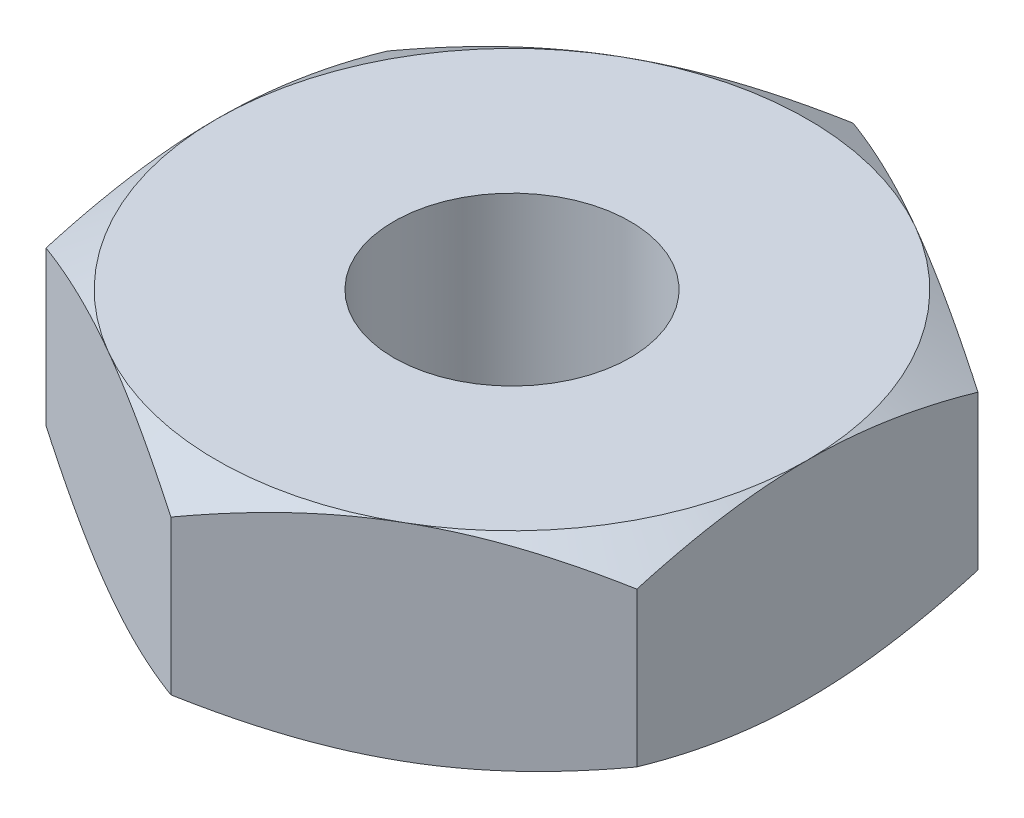
SolidWorks part; units mm, degrees
material "AISI 316 Stainless Steel Sheet (SS)"
ref_plane "Front Plane" through (0, 0, 0) normal (0, 0, 1) x (1, 0, 0)
ref_plane "Top Plane" through (0, 0, 0) normal (0, 1, 0) x (1, 0, 0)
ref_plane "Right Plane" through (0, 0, 0) normal (1, 0, 0) x (0, 0, -1)
sketch "Sketch1" plane through (0, 0, 0) normal (0, 1, 0) x (1, 0, 0)
  line L1 (-3.9688, 2.2914) -> (-3.9688, -2.2914)
  line L2 (-3.9688, -2.2914) -> (0, -4.5827)
  line L3 (0, -4.5827) -> (3.9687, -2.2914)
  line L4 (3.9687, -2.2914) -> (3.9688, 2.2914)
  line L5 (3.9688, 2.2914) -> (0, 4.5827)
  line L6 (0, 4.5827) -> (-3.9688, 2.2914)
  circle A0 centre (0, 0) radius 3.9688 construction
  circle A1 centre (0, 0) radius 1.5875
  dimension "Thread Size" = 3.175
  dimension "Hex" = 7.9375
extrude "Boss-Extrude1" add sketch "Sketch1" along normal mid plane 2.7781
sketch "Sketch2" plane through (0, 1.3891, 0) normal (0, 1, 0) x (1, 0, 0)
  circle A0 centre (0, 0) radius 1.5875 construction
  circle A1 centre (0, 0) radius 1.5875
curve "Helix/Spiral1" [suppressed] pitch 0.635 height 3.4131 turns 5.375 parameters "Pitch"=0.635
sketch "Sketch3" plane through (0, 0, 0) normal (1, 0, 0) x (0, 0, -1)
  line L0 (1.1751, 1.7066) -> (1.5875, 1.9447)
  line L1 (1.5875, 1.9447) -> (1.5875, 1.3891)
  line L2 (1.5875, 1.3891) -> (1.1751, 1.6272)
  line L3 (1.1751, 1.6272) -> (1.1751, 1.7066)
  line L4 (1.3813, 1.8256) -> (1.3813, 1.5081) construction
  line L5 (1.1751, 1.6669) -> (1.5875, 1.6669) construction
  line L6 (1.5875, 1.3891) -> (-1.5875, 1.3891) construction
  dimension "D1" = 60
  dimension "D2" = 0.0794
  dimension "D3" = 0.3175
sweep "Sweep1" [suppressed] add profiles "Sketch3" path "Helix/Spiral1"
sketch "Sketch4" plane through (0, 1.3891, 0) normal (0, 1, 0) x (1, 0, 0)
  circle A1 centre (0, 0) radius 1.5875
  circle A2 centre (0, 0) radius 1.5875
  dimension "D1" = 0
sketch "Sketch5" plane through (0, 1.3891, 0) normal (0, 1, 0) x (1, 0, 0)
  circle A0 centre (0, 0) radius 3.9688 construction
  circle A1 centre (0, 0) radius 3.9688
extrude "Cut-Extrude2" cut sketch "Sketch5" against normal through all draft 60 flip side to cut
mirror "Mirror1" about plane through (0, 0, 0) normal (0, 1, 0) of "Cut-Extrude2"
ref_axis "Axis1" through (0, -1.528, 0) along (0, 1, 0)
equation "\"D2@Sketch3\" = \"Pitch@Helix/Spiral1\"*.125"
equation "\"D3@Sketch3\" = \"Pitch@Helix/Spiral1\"*.5"
equation "\"D3@Helix/Spiral1\" = \"Height@Boss-Extrude1\"+\"Pitch@Helix/Spiral1\""
